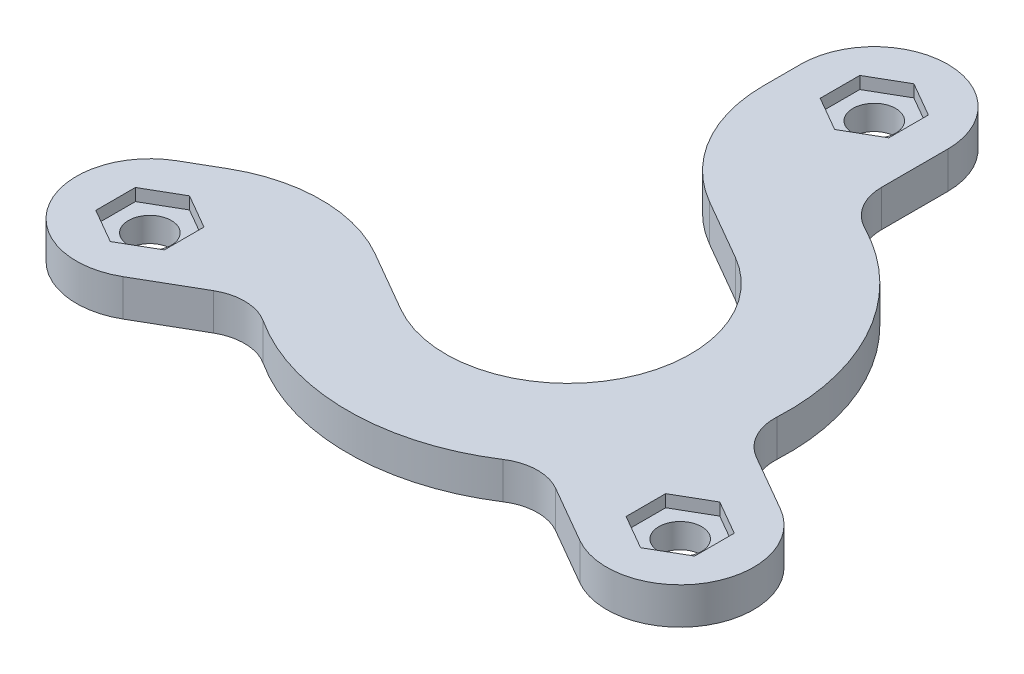
SolidWorks part; units mm, degrees
ref_plane "Front Plane" through (0, 0, 0) normal (0, 0, 1) x (1, 0, 0)
ref_plane "Top Plane" through (0, 0, 0) normal (0, 1, 0) x (1, 0, 0)
ref_plane "Right Plane" through (0, 0, 0) normal (1, 0, 0) x (0, 0, -1)
sketch "Sketch1" plane through (0, 0, 0) normal (0, 1, 0) x (1, 0, 0)
  line L0 (0, 0) -> (0, 9.0907) construction
  line L1 (0, 0) -> (7.1459, -4.1257) construction
  line L2 (0, 0) -> (-8.3205, -4.8039) construction
  line L3 (24.6506, -7.3038) -> (19.9706, -4.6018)
  line L4 (18.6506, -17.6962) -> (13.9706, -14.9941)
  line L5 (-18.6506, -17.6962) -> (-13.9706, -14.9941)
  line L6 (-24.6506, -7.3038) -> (-22, -5.7735)
  line L7 (-6, 25) -> (-6, 21.9393)
  line L8 (6, 25) -> (6, 19.5959)
  line L9 (-5, -8.6603) -> (-10, -5.7735)
  line L10 (-6, 25) -> (-6, 17.3205) [skipped]
  line L11 (-24.6506, -7.3038) -> (-18, -3.4641) [skipped]
  line L12 (5, 8.6603) -> (0, 11.547)
  line L13 (-5, -8.6603) -> (0, 0) construction
  line L14 (0, 0) -> (5, 8.6603) construction
  arc A0 (-5, -8.6603) -> (5, 8.6603) centre (0, 0) ccw
  arc A1 (17.9759, -0.9308) -> (8.1818, 16.033) centre (0, 0) ccw
  circle A2 centre (0, 25) radius 1.75
  circle A3 centre (0, 0) radius 25 construction
  circle A4 centre (21.6506, -12.5) radius 1.75
  circle A5 centre (-21.6506, -12.5) radius 1.75
  arc A6 (18.6506, -17.6962) -> (24.6506, -7.3038) centre (21.6506, -12.5) ccw
  arc A7 (-24.6506, -7.3038) -> (-18.6506, -17.6962) centre (-21.6506, -12.5) ccw
  arc A8 (6, 25) -> (-6, 25) centre (0, 25) ccw
  arc A9 (-10, -5.7735) -> (-22, -5.7735) centre (-16, -16.1658) ccw
  arc A10 (-9.7941, -15.1022) -> (9.7941, -15.1022) centre (0, 0) ccw
  arc A11 (0, 11.547) -> (-6, 21.9393) centre (6, 21.9393) cw
  arc A12 (-13.9706, -14.9941) -> (-9.7941, -15.1022) centre (-11.9706, -18.4582) cw
  arc A13 (13.9706, -14.9941) -> (9.7941, -15.1022) centre (11.9706, -18.4582) ccw
  arc A14 (19.9706, -4.6018) -> (17.9759, -0.9308) centre (21.9706, -1.1377) cw
  arc A15 (6, 19.5959) -> (8.1818, 16.033) centre (10, 19.5959) ccw
  point P36 (0, 0)
  dimension "D3" = 20
  dimension "D4" = 8
  dimension "D5" = 50
  dimension "D6" = 3.5
  dimension "D7" = 12
  dimension "D9" = 4
  dimension "D10" = 12
  dimension "D1" = 120
  dimension "D2" = 120
  dimension "D8" = 3
extrude "Boss-Extrude1" add sketch "Sketch1" along normal blind 3
sketch "Sketch2" plane through (0, 3, 0) normal (0, 1, 0) x (1, 0, 0)
  line L1 (2.8, 23.3834) -> (2.8, 26.6166)
  line L2 (2.8, 26.6166) -> (0, 28.2332)
  line L3 (0, 28.2332) -> (-2.8, 26.6166)
  line L4 (-2.8, 26.6166) -> (-2.8, 23.3834)
  line L5 (-2.8, 23.3834) -> (0, 21.7668)
  line L6 (0, 21.7668) -> (2.8, 23.3834)
  line L7 (24.4506, -14.1166) -> (24.4506, -10.8834)
  line L8 (24.4506, -10.8834) -> (21.6506, -9.2668)
  line L9 (21.6506, -9.2668) -> (18.8506, -10.8834)
  line L10 (18.8506, -10.8834) -> (18.8506, -14.1166)
  line L11 (18.8506, -14.1166) -> (21.6506, -15.7332)
  line L12 (21.6506, -15.7332) -> (24.4506, -14.1166)
  line L13 (-24.4506, -14.1166) -> (-21.6506, -15.7332)
  line L14 (-21.6506, -15.7332) -> (-18.8506, -14.1166)
  line L15 (-18.8506, -14.1166) -> (-18.8506, -10.8834)
  line L16 (-18.8506, -10.8834) -> (-21.6506, -9.2668)
  line L17 (-21.6506, -9.2668) -> (-24.4506, -10.8834)
  line L18 (-24.4506, -10.8834) -> (-24.4506, -14.1166)
  circle A0 centre (0, 25) radius 2.8 construction
  circle A1 centre (21.6506, -12.5) radius 2.8 construction
  circle A2 centre (-21.6506, -12.5) radius 2.8 construction
  dimension "D1" = 5.6
extrude "Cut-Extrude1" cut sketch "Sketch2" against normal blind 1
